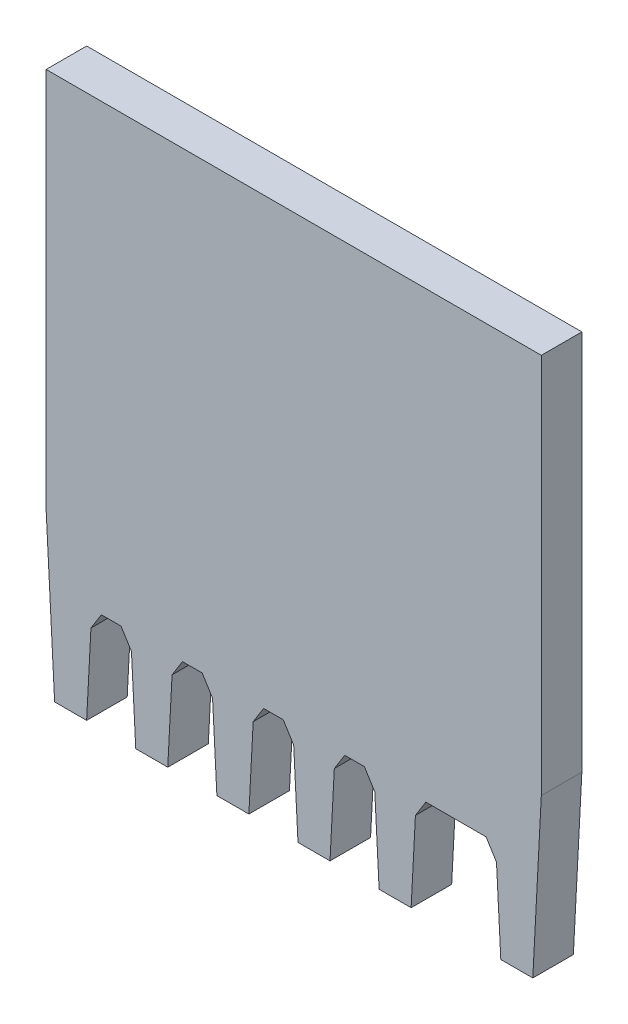
SolidWorks part; units mm, degrees
ref_plane "Front Plane" through (0, 0, 0) normal (0, 0, 1) x (1, 0, 0)
ref_plane "Top Plane" through (0, 0, 0) normal (0, 1, 0) x (1, 0, 0)
ref_plane "Right Plane" through (0, 0, 0) normal (1, 0, 0) x (0, 0, -1)
sketch "Sketch1" plane through (0, 0, 0) normal (0, 0, 1) x (1, 0, 0)
  line L0 (0, 0) -> (0, 20.1) construction
  line L1 (0, 20.1) -> (18.3124, 20.1) construction
  line L2 (18.3124, 20.1) -> (18.3124, 0) construction
  line L3 (18.3124, 0) -> (0, 0) construction
  line L4 (0, 3) -> (18.3124, 3) construction
  line L5 (0, 6) -> (18.3124, 6) construction
  line L6 (0.9062, 6) -> (0.9062, 0) construction
  line L7 (3.9062, 6) -> (3.9062, 0) construction
  line L8 (6.9062, 6) -> (6.9062, 0) construction
  line L9 (9.9062, 6) -> (9.9062, 0) construction
  line L10 (12.9062, 6) -> (12.9062, 0) construction
  line L11 (17.4062, 6) -> (17.4062, 0) construction
  line L12 (0.9062, 3) -> (3.9062, 3) construction
  line L13 (3.9062, 3) -> (6.9062, 3) construction
  line L14 (6.9062, 3) -> (9.9062, 3) construction
  line L15 (9.9062, 3) -> (12.9062, 3) construction
  line L16 (12.9062, 3) -> (17.4062, 3) construction
  line L17 (0.9062, 3) -> (0, 3) construction
  line L18 (17.4062, 3) -> (18.3124, 3) construction
  line L19 (2.4062, 3) -> (2.4062, 0) construction
  line L20 (5.4062, 3) -> (5.4062, 0) construction
  line L21 (8.4062, 3) -> (8.4062, 0) construction
  line L22 (11.4062, 3) -> (11.4062, 0) construction
  line L23 (15.1562, 3) -> (15.1562, 0) construction
  line L24 (14.4062, 3.75) -> (15.9062, 3.75) construction
  line L25 (0, 6) -> (0.3144, 0)
  line L26 (0.3144, 0) -> (1.4979, 0)
  line L27 (1.4979, 0) -> (1.6572, 3.0393)
  line L28 (3.1552, 3.0393) -> (3.3144, 0)
  line L29 (3.3144, 0) -> (4.4979, 0)
  line L30 (4.4979, 0) -> (4.6572, 3.0393)
  line L31 (6.1552, 3.0393) -> (6.3144, 0)
  line L32 (6.3144, 0) -> (7.4979, 0)
  line L33 (7.4979, 0) -> (7.6572, 3.0393)
  line L34 (9.1552, 3.0393) -> (9.3144, 0)
  line L35 (9.3144, 0) -> (10.4979, 0)
  line L36 (10.4979, 0) -> (10.6572, 3.0393)
  line L37 (12.1552, 3.0393) -> (12.3144, 0)
  line L38 (12.3144, 0) -> (13.4979, 0)
  line L39 (13.4979, 0) -> (13.6572, 3.0393)
  line L40 (16.6552, 3.0393) -> (16.8144, 0)
  line L41 (16.8144, 0) -> (17.9979, 0)
  line L42 (17.9979, 0) -> (18.3124, 6)
  line L44 (1.6572, 3.0393) -> (2.0426, 3.656)
  line L45 (0, 6) -> (0, 20.1)
  line L46 (0, 20.1) -> (18.3124, 20.1)
  line L47 (18.3124, 20.1) -> (18.3124, 6)
  line L48 (9.1562, 20.1) -> (9.1562, 6) construction
  line L49 (2.0426, 3.656) -> (2.7698, 3.656)
  line L50 (2.7698, 3.656) -> (3.1552, 3.0393)
  line L51 (4.6572, 3.0393) -> (5.0426, 3.656)
  line L52 (5.0426, 3.656) -> (5.7698, 3.656)
  line L53 (5.7698, 3.656) -> (6.1552, 3.0393)
  line L54 (7.6572, 3.0393) -> (8.0426, 3.656)
  line L55 (8.0426, 3.656) -> (8.7698, 3.656)
  line L56 (8.7698, 3.656) -> (9.1552, 3.0393)
  line L57 (10.6572, 3.0393) -> (11.0426, 3.656)
  line L58 (11.0426, 3.656) -> (11.7698, 3.656)
  line L59 (11.7698, 3.656) -> (12.1552, 3.0393)
  line L60 (13.6572, 3.0393) -> (14.0426, 3.656)
  line L61 (14.0426, 3.656) -> (16.2698, 3.656)
  line L62 (16.2698, 3.656) -> (16.6552, 3.0393)
  arc A0 (3.1552, 3.0393) -> (1.6572, 3.0393) centre (2.4062, 3) ccw construction
  arc A1 (6.1552, 3.0393) -> (4.6572, 3.0393) centre (5.4062, 3) ccw construction
  arc A2 (9.1552, 3.0393) -> (7.6572, 3.0393) centre (8.4062, 3) ccw construction
  arc A3 (12.1552, 3.0393) -> (10.6572, 3.0393) centre (11.4062, 3) ccw construction
  arc A4 (13.6572, 3.0393) -> (14.4062, 3.75) centre (14.4062, 3) cw construction
  arc A5 (16.6552, 3.0393) -> (15.9062, 3.75) centre (15.9062, 3) ccw construction
  dimension "D7" = 0.75
  dimension "D1" = 3
  dimension "D2" = 6
  dimension "D3" = 14.1
  dimension "D4" = 3
  dimension "D6" = 4.5
  dimension "D8" = 3
  dimension "D9" = 18.3124
  dimension "D10" = 20.1
extrude "Boss-Extrude1" add sketch "Sketch1" along normal blind 1.5
sketch "Sketch3" plane through (0, 0, 0) normal (0, 0, 1) x (1, 0, 0)
  line L0 (-0.4005, 6) -> (18.7129, 6)
  line L1 (18.7129, 3) -> (-0.4005, 3) construction
  line L2 (-0.4005, 0) -> (18.7129, 0) construction
  line L3 (-0.4005, -0.5) -> (18.7129, -0.5) construction
  line L4 (18.7129, -0.5) -> (18.7129, 6) construction
  line L5 (-0.4005, 6) -> (-0.4005, -0.5) construction
  line L6 (18.3124, 0) -> (0, 0) construction
  line L7 (0, 3) -> (18.3124, 3) construction
  line L8 (0, 6) -> (18.3124, 6) construction
  line L9 (0.3407, -0.5) -> (0, 6) construction
  line L10 (18.3124, 6) -> (17.9717, -0.5) construction
  line L11 (17.9979, 0) -> (18.3124, 6) construction
  line L12 (0, 6) -> (0.3144, 0) construction
  line L13 (5.4062, 6) -> (5.4062, -0.5) construction
  line L14 (3.9062, 6) -> (3.9062, -0.5) construction
  line L15 (5.4062, 3) -> (5.4062, 0) construction
  line L16 (3.1572, 3) -> (3.3407, -0.5) construction
  line L17 (2.7567, 3) -> (2.9401, -0.5)
  line L18 (3.1552, 3.0393) -> (3.3144, 0) construction
  line L19 (2.9401, -0.5) -> (4.8723, -0.5)
  line L20 (4.8723, -0.5) -> (5.0557, 3)
  line L21 (2.8484, 1.25) -> (3.2478, 1.2709) construction
  line L22 (5.9401, -0.5) -> (5.7567, 3)
  line L26 (7.8723, -0.5) -> (5.9401, -0.5)
  line L27 (8.0557, 3) -> (7.8723, -0.5)
  line L30 (2.4062, -0.5) -> (2.4062, 6) construction
  line L31 (2.4062, 3) -> (2.4062, 0) construction
  line L32 (8.4062, 6) -> (8.4062, -0.5) construction
  line L34 (11.4062, -0.5) -> (11.4062, 6) construction
  line L35 (15.1562, -0.5) -> (15.1562, 6) construction
  line L36 (8.4062, 3) -> (8.4062, 0) construction
  line L37 (11.4062, 3) -> (11.4062, 0) construction
  line L38 (15.1562, 3) -> (15.1562, 0) construction
  line L39 (10.8723, -0.5) -> (11.0557, 3)
  line L40 (8.9401, -0.5) -> (10.8723, -0.5)
  line L41 (8.7567, 3) -> (8.9401, -0.5)
  line L42 (11.9401, -0.5) -> (11.7567, 3)
  line L43 (13.8723, -0.5) -> (11.9401, -0.5)
  line L44 (14.0557, 3) -> (13.8723, -0.5)
  line L45 (16.4401, -0.5) -> (18.3723, -0.5)
  line L46 (16.2567, 3) -> (16.4401, -0.5)
  line L47 (18.3723, -0.5) -> (18.7129, 6)
  line L48 (1.8723, -0.5) -> (-0.0599, -0.5)
  line L49 (2.0557, 3) -> (1.8723, -0.5)
  line L50 (-0.0599, -0.5) -> (-0.4005, 6)
  line L51 (16.2567, 3) -> (14.0557, 3)
  line L52 (11.7567, 3) -> (11.0557, 3)
  line L53 (8.7567, 3) -> (8.0557, 3)
  line L54 (5.7567, 3) -> (5.0557, 3)
  line L55 (2.7567, 3) -> (2.0557, 3)
  dimension "D1" = 0.5
  dimension "D2" = 0.4
ref_plane "Plane1" through (3.9062, 0, 0) normal (1, 0, 0) x (0, 0, -1)
sketch "Sketch4" plane through (3.9062, 0, 0) normal (1, 0, 0) x (0, 0, -1)
  line L0 (0, 6) -> (0, -0.5) construction
  line L1 (0.6, 6) -> (-2.1, 6) construction
  line L2 (0.6, 6) -> (0.6, -0.5) construction
  line L3 (0.6, -0.5) -> (-2.1, -0.5) construction
  line L4 (-2.1, 6) -> (-2.1, -0.5) construction
  line L5 (-0.75, -0.5) -> (-0.75, 6) construction
  line L6 (-1.5, 6) -> (-1.5, -0.5) construction
  line L7 (0.6, 2.4005) -> (-2.1, 2.4005) construction
  line L8 (0.3, 6) -> (0.3, -0.5) construction
  line L9 (0.6, 2.4005) -> (3.846, 6) construction
  line L10 (2.2302, 6) -> (0.6, 4.1923) construction
  line L11 (0.6, 4.1923) -> (1.7139, 3.1878) construction
  line L12 (1.7139, 3.1878) -> (4.25, 6)
  line L13 (4.25, 6) -> (0.6, 6) construction
  line L14 (0.3, 1) -> (-1.8, 1) construction
  line L15 (-2.1, 0) -> (0.6, 0) construction
  line L16 (1.7139, 3.1878) -> (1.4912, 3.3887)
  line L17 (1.4912, 3.3887) -> (0.6, 2.4005)
  line L18 (-3.2139, 3.1878) -> (-5.75, 6)
  line L19 (-3.2139, 3.1878) -> (-2.9912, 3.3887)
  line L20 (-2.9912, 3.3887) -> (-2.1, 2.4005)
  line L21 (-2.1, 6) -> (-5.75, 6) construction
  line L22 (0.6, 3.0724) -> (3.2401, 6) construction
  arc A0 (0.4965, 2.2224) -> (0.6, -0.5) centre (4.2, 1) ccw
  arc A1 (0.6, 2.4005) -> (0.4965, 2.2224) centre (0.9713, 2.0656) ccw
  arc A2 (-2.1, 2.4005) -> (-1.9965, 2.2224) centre (-2.4713, 2.0656) cw
  arc A3 (-1.9965, 2.2224) -> (-2.1, -0.5) centre (-5.7, 1) cw
  dimension "D6" = 0.5
  dimension "D1" = 0.6
  dimension "D2" = 0.3
  dimension "D3" = 1.5
  dimension "D4" = 1
  dimension "D5" = 0.3
  dimension "D7" = 10
sketch "Sketch5" plane through (0, 0, 0) normal (1, 0, 0) x (0, 0, -1)
  line L0 (2.2302, 6) -> (0.6, 4.1923) construction
  line L1 (0.6, 4.1923) -> (1.7139, 3.1878) construction
  line L2 (1.7139, 3.1878) -> (4.25, 6) construction
  line L3 (2.2302, 6) -> (0.6, 4.1923) construction
  line L4 (0.6, 4.1923) -> (1.7139, 3.1878) construction
  line L5 (1.7139, 3.1878) -> (4.25, 6) construction
ref_plane "Plane2" through (0, 2.6105, -2.3541) normal (0, 0.7426, -0.6697) x (1, 0, 0)
sketch "Sketch6" plane through (0, 2.6105, -2.3541) normal (0, 0.7426, -0.6697) x (1, 0, 0)
  line L1 (3.9062, -2.362) -> (3.9062, -0.862) construction
  line L2 (3.9062, -2.362) -> (3.9062, -5.0612) construction
  line L3 (4.6562, -5.0612) -> (3.1562, -5.0612)
  line L4 (4.6562, -1.612) -> (3.1562, -1.612) construction
  line L5 (3.1562, -1.612) -> (3.1562, -5.0612)
  line L6 (4.6562, -1.612) -> (4.6562, -5.0612)
  line L10 (2.4062, -5.0612) -> (15.1562, -5.0612) construction
  line L11 (15.1562, -5.0612) -> (15.1562, -0.862) construction
  line L12 (15.1562, -0.862) -> (2.4062, -0.862) construction
  line L13 (2.4062, -0.862) -> (2.4062, -5.0612) construction
  line L14 (15.1562, 0.3349) -> (15.1562, -4.0182) construction
  line L15 (2.4062, 0.3349) -> (2.4062, -4.0182) construction
  line L16 (11.4062, -5.0612) -> (11.4062, -0.862) construction
  line L17 (8.4062, -5.0612) -> (8.4062, -0.862) construction
  line L18 (5.4062, -5.0612) -> (5.4062, -0.862) construction
  line L19 (5.4062, -4.0182) -> (5.4062, 0.3349) construction
  line L20 (8.4062, -4.0182) -> (8.4062, 0.3349) construction
  line L21 (11.4062, 0.3349) -> (11.4062, -4.0182) construction
  line L22 (0.1562, -1.612) -> (0.1562, -5.0612)
  line L23 (0.1562, -5.0612) -> (1.6562, -5.0612)
  line L24 (1.6562, -1.612) -> (1.6562, -5.0612)
  line L25 (7.6562, -1.612) -> (7.6562, -5.0612)
  line L26 (6.1562, -5.0612) -> (7.6562, -5.0612)
  line L27 (6.1562, -1.612) -> (6.1562, -5.0612)
  line L28 (10.6562, -1.612) -> (10.6562, -5.0612)
  line L29 (10.6562, -5.0612) -> (9.1562, -5.0612)
  line L30 (9.1562, -1.612) -> (9.1562, -5.0612)
  line L31 (13.6562, -1.612) -> (13.6562, -5.0612)
  line L32 (12.1562, -5.0612) -> (13.6562, -5.0612)
  line L33 (12.1562, -1.612) -> (12.1562, -5.0612)
  line L34 (18.1562, -1.612) -> (18.1562, -5.0612)
  line L35 (18.1562, -5.0612) -> (16.6562, -5.0612)
  line L36 (16.6562, -1.612) -> (16.6562, -5.0612)
  circle A0 centre (3.9062, -1.612) radius 0.75 construction
  arc A1 (4.6562, -1.612) -> (3.1562, -1.612) centre (3.9062, -1.612) ccw
  arc A2 (0.1562, -1.612) -> (1.6562, -1.612) centre (0.9062, -1.612) cw
  arc A3 (6.1562, -1.612) -> (7.6562, -1.612) centre (6.9062, -1.612) cw
  arc A4 (10.6562, -1.612) -> (9.1562, -1.612) centre (9.9062, -1.612) ccw
  arc A5 (12.1562, -1.612) -> (13.6562, -1.612) centre (12.9062, -1.612) cw
  arc A6 (18.1562, -1.612) -> (16.6562, -1.612) centre (17.4062, -1.612) ccw
ref_plane "Plane3" through (0, 1.6223, -1.463) normal (0, 0.7426, -0.6697) x (1, 0, 0)
sketch "Sketch7" plane through (0, 1.6223, -1.463) normal (0, 0.7426, -0.6697) x (1, 0, 0)
  line L0 (3.1562, -1.612) -> (3.1562, -5.0612) construction
  line L1 (4.6562, -5.0612) -> (3.1562, -5.0612) construction
  line L2 (4.6562, -1.612) -> (4.6562, -5.0612) construction
  line L3 (3.1562, -1.612) -> (3.1562, -5.0612) construction
  line L4 (4.6562, -5.0612) -> (3.1562, -5.0612) construction
  line L5 (4.6562, -1.612) -> (4.6562, -5.0612) construction
  line L6 (3.9062, -0.862) -> (3.9062, -5.0612) construction
  line L7 (4.6562, -1.612) -> (3.1562, -1.612) construction
  line L8 (4.6562, -2.362) -> (3.1562, -2.362) construction
  line L9 (3.4562, -1.612) -> (3.4562, -2.362)
  line L10 (3.4562, -2.362) -> (4.3562, -2.362)
  line L11 (4.3562, -2.362) -> (4.3562, -1.612)
  line L12 (2.4062, -0.862) -> (2.4062, -5.0612) construction
  line L13 (2.4062, -5.0612) -> (15.1562, -5.0612) construction
  line L14 (15.1562, -0.862) -> (2.4062, -0.862) construction
  line L15 (5.4062, -5.0612) -> (5.4062, -0.862) construction
  line L16 (8.4062, -5.0612) -> (8.4062, -0.862) construction
  line L17 (11.4062, -5.0612) -> (11.4062, -0.862) construction
  line L18 (15.1562, -5.0612) -> (15.1562, -0.862) construction
  line L19 (2.4062, -0.862) -> (2.4062, -5.0612) construction
  line L20 (2.4062, -5.0612) -> (15.1562, -5.0612) construction
  line L21 (15.1562, -0.862) -> (2.4062, -0.862) construction
  line L22 (5.4062, -5.0612) -> (5.4062, -0.862) construction
  line L23 (8.4062, -5.0612) -> (8.4062, -0.862) construction
  line L24 (11.4062, -5.0612) -> (11.4062, -0.862) construction
  line L25 (15.1562, -5.0612) -> (15.1562, -0.862) construction
  line L26 (0.4562, -2.362) -> (0.4562, -1.612)
  line L27 (1.3562, -2.362) -> (0.4562, -2.362)
  line L28 (1.3562, -1.612) -> (1.3562, -2.362)
  line L29 (7.3562, -2.362) -> (6.4562, -2.362)
  line L30 (7.3562, -1.612) -> (7.3562, -2.362)
  line L31 (6.4562, -2.362) -> (6.4562, -1.612)
  line L32 (9.4562, -1.612) -> (9.4562, -2.362)
  line L33 (10.3562, -2.362) -> (10.3562, -1.612)
  line L34 (9.4562, -2.362) -> (10.3562, -2.362)
  line L35 (13.3562, -1.612) -> (13.3562, -2.362)
  line L36 (12.4562, -2.362) -> (12.4562, -1.612)
  line L37 (13.3562, -2.362) -> (12.4562, -2.362)
  line L38 (16.9562, -1.612) -> (16.9562, -2.362)
  line L39 (17.8562, -2.362) -> (17.8562, -1.612)
  line L40 (16.9562, -2.362) -> (17.8562, -2.362)
  arc A0 (4.6562, -1.612) -> (3.1562, -1.612) centre (3.9062, -1.612) ccw construction
  arc A1 (4.6562, -1.612) -> (3.1562, -1.612) centre (3.9062, -1.612) ccw construction
  circle A2 centre (3.9062, -1.612) radius 0.45 construction
  arc A3 (4.3562, -1.612) -> (3.4562, -1.612) centre (3.9062, -1.612) ccw
  arc A4 (0.4562, -1.612) -> (1.3562, -1.612) centre (0.9062, -1.612) cw
  arc A5 (6.4562, -1.612) -> (7.3562, -1.612) centre (6.9062, -1.612) cw
  arc A6 (10.3562, -1.612) -> (9.4562, -1.612) centre (9.9062, -1.612) ccw
  arc A7 (12.4562, -1.612) -> (13.3562, -1.612) centre (12.9062, -1.612) cw
  arc A8 (17.8562, -1.612) -> (16.9562, -1.612) centre (17.4062, -1.612) ccw
ref_plane "bisect" through (0, 0, 0.75) normal (0, 0, 1) x (1, 0, 0)
ref_plane "insert_surface" through (0, 6, 0) normal (0, 1, 0) x (1, 0, 0)
sketch "Sketch8" plane through (0, 6, 0) normal (0, 1, 0) x (1, 0, 0)
  line L0 (18.7129, -0.75) -> (-0.4005, -0.75) construction
  line L1 (-0.4005, 0.6) -> (18.7129, 0.6)
  line L2 (-0.4005, 0.6) -> (-0.4005, -2.1)
  line L3 (-0.4005, -2.1) -> (18.7129, -2.1)
  line L4 (18.7129, 0.6) -> (18.7129, -2.1)
  line L5 (9.1562, 0.6) -> (9.1562, -2.1) construction
  line L6 (0, 0) -> (18.3124, 0) construction
  line L7 (0, 0) -> (0, -1.5) construction
  line L8 (0, -1.5) -> (18.3124, -1.5) construction
  line L9 (18.3124, 0) -> (18.3124, -1.5) construction
  line L10 (18.7129, 0.3) -> (-0.4005, 0.3) construction
  line L11 (18.7129, -1.8) -> (-0.4005, -1.8) construction
sketch "Sketch9" plane through (0, 0, 0) normal (0, 0, 1) x (1, 0, 0)
  line L0 (18.3723, -0.5) -> (18.7129, 6) construction
  line L1 (-0.4005, 6) -> (18.7129, 6) construction
  line L2 (-0.0599, -0.5) -> (-0.4005, 6) construction
  line L3 (1.8723, -0.5) -> (-0.0599, -0.5) construction
  line L4 (2.0557, 3) -> (1.8723, -0.5) construction
  line L5 (2.7567, 3) -> (2.0557, 3) construction
  line L6 (2.7567, 3) -> (2.9401, -0.5) construction
  line L7 (2.9401, -0.5) -> (4.8723, -0.5) construction
  line L8 (4.8723, -0.5) -> (5.0557, 3) construction
  line L9 (5.7567, 3) -> (5.0557, 3) construction
  line L10 (5.9401, -0.5) -> (5.7567, 3) construction
  line L11 (7.8723, -0.5) -> (5.9401, -0.5) construction
  line L12 (8.0557, 3) -> (7.8723, -0.5) construction
  line L13 (8.7567, 3) -> (8.0557, 3) construction
  line L14 (8.7567, 3) -> (8.9401, -0.5) construction
  line L15 (8.9401, -0.5) -> (10.8723, -0.5) construction
  line L16 (10.8723, -0.5) -> (11.0557, 3) construction
  line L17 (11.7567, 3) -> (11.0557, 3) construction
  line L18 (11.9401, -0.5) -> (11.7567, 3) construction
  line L19 (13.8723, -0.5) -> (11.9401, -0.5) construction
  line L20 (14.0557, 3) -> (13.8723, -0.5) construction
  line L21 (16.2567, 3) -> (14.0557, 3) construction
  line L22 (16.2567, 3) -> (16.4401, -0.5) construction
  line L23 (16.4401, -0.5) -> (18.3723, -0.5) construction
  line L24 (18.3723, -0.5) -> (18.7129, 6)
  line L25 (-0.4005, 6) -> (18.7129, 6) construction
  line L26 (-0.0599, -0.5) -> (-0.4005, 6)
  line L27 (1.8723, -0.5) -> (-0.0599, -0.5)
  line L28 (2.0557, 3) -> (1.8723, -0.5)
  line L29 (2.7567, 3) -> (2.0557, 3) construction
  line L30 (2.7567, 3) -> (2.9401, -0.5)
  line L31 (2.9401, -0.5) -> (4.8723, -0.5)
  line L32 (4.8723, -0.5) -> (5.0557, 3)
  line L33 (5.7567, 3) -> (5.0557, 3) construction
  line L34 (5.9401, -0.5) -> (5.7567, 3)
  line L35 (7.8723, -0.5) -> (5.9401, -0.5)
  line L36 (8.0557, 3) -> (7.8723, -0.5)
  line L37 (8.7567, 3) -> (8.0557, 3) construction
  line L38 (8.7567, 3) -> (8.9401, -0.5)
  line L39 (8.9401, -0.5) -> (10.8723, -0.5)
  line L40 (10.8723, -0.5) -> (11.0557, 3)
  line L41 (11.7567, 3) -> (11.0557, 3) construction
  line L42 (11.9401, -0.5) -> (11.7567, 3)
  line L43 (13.8723, -0.5) -> (11.9401, -0.5)
  line L44 (14.0557, 3) -> (13.8723, -0.5)
  line L45 (16.2567, 3) -> (14.0557, 3) construction
  line L46 (16.2567, 3) -> (16.4401, -0.5)
  line L47 (16.4401, -0.5) -> (18.3723, -0.5)
  line L48 (16.2567, 3) -> (16.2567, 6)
  line L49 (14.0557, 3) -> (14.0557, 6)
  line L50 (11.7567, 3) -> (11.7567, 6)
  line L51 (18.7129, 6) -> (-0.4005, 6) construction
  line L52 (11.0557, 3) -> (11.0557, 6)
  line L53 (-0.4005, 6) -> (18.7129, 6) construction
  line L54 (8.7567, 3) -> (8.7567, 6)
  line L55 (8.0557, 3) -> (8.0557, 6)
  line L58 (5.7567, 3) -> (5.7567, 6)
  line L60 (5.0557, 3) -> (5.0557, 6)
  line L62 (15.1562, -0.5) -> (15.1562, 6) construction
  line L63 (15.1562, -0.5) -> (15.1562, 6) construction
  line L64 (2.7567, 3) -> (2.7567, 6)
  line L65 (2.0557, 3) -> (2.0557, 6)
  line L67 (18.7129, 6) -> (16.2567, 6)
  line L68 (14.0557, 6) -> (11.7567, 6)
  line L69 (11.0557, 6) -> (8.7567, 6)
  line L70 (8.0557, 6) -> (5.7567, 6)
  line L71 (5.0557, 6) -> (2.7567, 6)
  line L72 (2.0557, 6) -> (-0.4005, 6)
sketch "Sketch10" plane through (0, 6, 0) normal (0, 1, 0) x (1, 0, 0)
  line L0 (9.1562, -0.75) -> (9.1562, -5.75) construction
  line L1 (-0.8438, 4.25) -> (19.1562, 4.25)
  line L2 (-0.8438, 4.25) -> (-0.8438, -5.75)
  line L3 (-0.8438, -5.75) -> (19.1562, -5.75)
  line L4 (19.1562, 4.25) -> (19.1562, -5.75)
  line L6 (9.1562, -0.75) -> (9.1562, 4.25) construction
  line L7 (9.1562, -0.75) -> (19.1562, -0.75) construction
  line L8 (9.1562, -0.75) -> (-0.8438, -0.75) construction
  line L9 (-10.5124, -0.75) -> (10.5124, -0.75) construction
  dimension "D1" = 20
  dimension "D2" = 10
